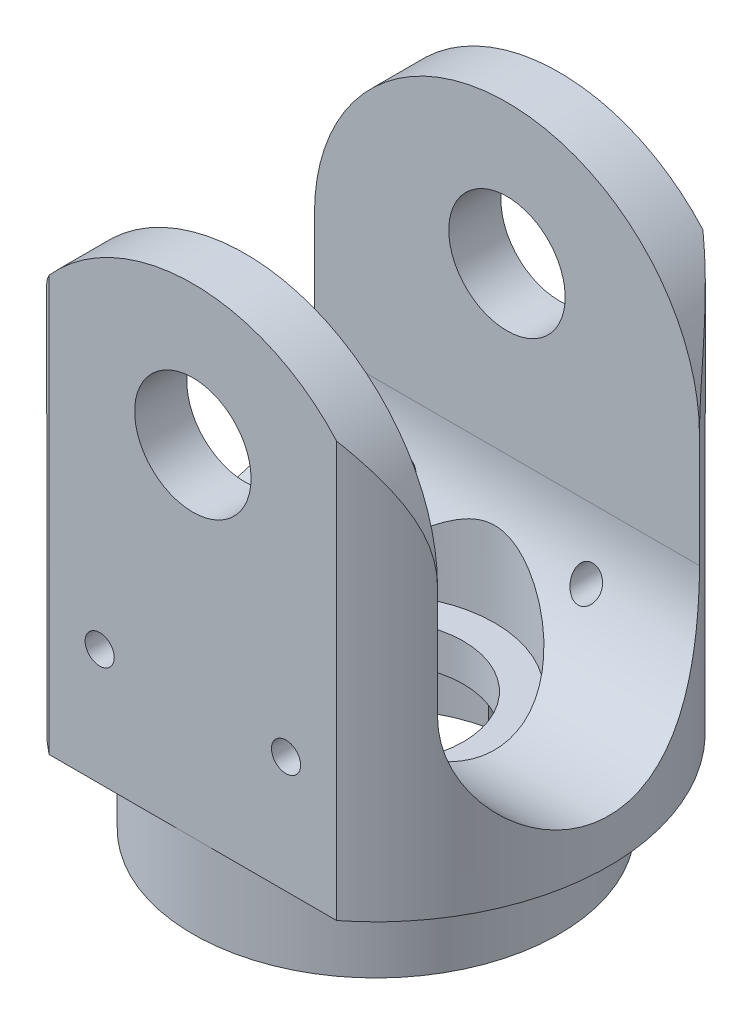
SolidWorks part; units mm, degrees
material "7075-T6 (SN)"
ref_plane "X-Y Datum" through (0, 0, 0) normal (0, 0, 1) x (1, 0, 0)
ref_plane "X-Z Datum" through (0, 0, 0) normal (0, 1, 0) x (1, 0, 0)
ref_plane "Y-Z Datum" through (0, 0, 0) normal (1, 0, 0) x (0, 0, -1)
sketch "Sketch1" plane through (0, 0, 0) normal (0, 1, 0) x (1, 0, 0)
  circle A0 centre (0, 0) radius 12.7
  dimension "D1" = 25.4
extrude "Boss-Extrude1" add sketch "Sketch1" along normal blind 15.367 and the other way blind 15.367
ref_plane "Plane2" through (0, 0, 9.9886) normal (0, 0, 1) x (1, 0, 0)
sketch "Sketch4" plane through (0, 0, 9.9886) normal (0, 0, 1) x (1, 0, 0)
  line L1 (-12.7, 15.367) -> (12.7, 15.367)
  line L2 (-12.7, 15.367) -> (-12.7, -15.367)
  line L3 (-12.7, -15.367) -> (12.7, -15.367)
  line L4 (12.7, 15.367) -> (12.7, -15.367)
extrude "Cut-Extrude2" cut sketch "Sketch4" along normal through all
mirror "Mirror2" about plane through (0, 0, 0) normal (0, 0, 1) of "Cut-Extrude2"
sketch "Sketch5" plane through (0, 0, 0) normal (1, 0, 0) x (0, 0, -1)
  line L0 (9.9886, 15.367) -> (-9.9886, 15.367) construction
  line L1 (-7.1437, 15.367) -> (7.1437, 15.367)
  line L2 (-7.1437, 15.367) -> (-7.1437, -1.27)
  line L3 (-7.1437, -1.27) -> (7.1438, -1.27)
  line L4 (7.1437, 15.367) -> (7.1438, -1.27)
  line L5 (0, 13.97) -> (0, -13.97) construction
  line L6 (0, -8.4138) -> (0, 15.367) construction
  arc A0 (-7.1437, -1.27) -> (7.1438, -1.27) centre (0, -1.27) ccw
  dimension "D3" = 16.637
  dimension "D4" = 23.7808
  dimension "D1" = 14.2875
  dimension "D2" = 7.1437
extrude "Cut-Extrude3" cut sketch "Sketch5" against normal through all both and the other way through all contours L6 A0 L3 | A0 L6 L3 | L2 L1 L4 L3 region at (0, -4.3019, 3.0319) region at (0, -4.3019, -3.0319)
sketch "Sketch6" plane through (0, 0, 9.9886) normal (0, 0, 1) x (1, 0, 0)
  line L0 (0, -43.0151) -> (0, 43.0151) construction
  line L1 (-7.8434, 15.367) -> (7.8434, 15.367) construction
  line L2 (10.5004, 4.8666) -> (14.8497, 4.8666)
  line L3 (-10.5004, 4.8666) -> (-14.8497, 4.8666)
  circle A0 centre (0, 4.8666) radius 10.5004
  arc A1 (14.8497, 4.8666) -> (-14.8497, 4.8666) centre (0, 4.8666) ccw
  line M2 (7.8434, 15.367) -> (-7.8434, 15.367)
  line M3 (-7.8434, 15.367) -> (-7.8434, -15.367)
  line M5 (7.8434, -15.367) -> (7.8434, 15.367)
  dimension "D1" = 21.0007
extrude "Cut-Extrude4" cut sketch "Sketch6" against normal through all contours L2 A1 L3 A0 M3 M2 M5 | A0 M2 M3 | A0 M5 M2 region at (10.124, 8.7197, 9.9886) region at (5.9543, 14.3505, 9.9886) region at (-5.9543, 14.3505, 9.9886)
sketch "Sketch7" plane through (0, -15.367, 0) normal (0, -1, 0) x (1, 0, 0)
  circle A0 centre (0, 0) radius 4.7625
  dimension "D1" = 9.525
extrude "Cut-Extrude5" cut sketch "Sketch7" against normal through all
sketch "Sketch9" plane through (0, -15.367, 0) normal (0, -1, 0) x (1, 0, 0)
  circle A0 centre (0, 0) radius 9.9822
  circle A1 centre (0, 0) radius 17.8528
  dimension "D1" = 19.9644
extrude "Cut-Extrude6" cut sketch "Sketch9" against normal blind 4.572
ref_plane "Plane3" through (0, 15.367, 0) normal (0, 1, 0) x (1, 0, 0)
sketch "Sketch10" plane through (0, 15.367, 0) normal (0, 1, 0) x (1, 0, 0)
  circle A0 centre (0, 0) radius 6.477
  dimension "D1" = 12.954
extrude "Cut-Extrude7" cut sketch "Sketch10" against normal blind 24.257
sketch "Sketch11" plane through (0, 0, 9.9886) normal (0, 0, 1) x (1, 0, 0)
  line L0 (-9.9822, -10.795) -> (9.9822, -10.795) construction
  line L1 (0, 7.747) -> (0, 0) construction
  circle A0 centre (0, 7.747) radius 3.175
  dimension "D1" = 6.35
  dimension "D2" = 18.542
extrude "Cut-Extrude8" cut sketch "Sketch11" against normal through all
sketch "Sketch12" plane through (0, 0, -9.9886) normal (0, 0, -1) x (-1, 0, 0)
  line L0 (-7.8434, -10.795) -> (7.8434, -10.795) construction
  line L1 (7.8434, 11.848) -> (7.8434, -10.795) construction
  line L2 (-7.8434, -10.795) -> (-7.8434, 11.848) construction
  circle A0 centre (5.0811, -4.445) radius 0.7938
  circle A1 centre (-5.0811, -4.445) radius 0.7938
  point P6 (-5.8749, -4.445)
  point P7 (5.8749, -4.445)
  dimension "D1" = 1.5875
  dimension "D2" = 1.5875
  dimension "D3" = 6.35
  dimension "D4" = 6.35
  dimension "D5" = 1.9685
  dimension "D6" = 1.9685
extrude "Cut-Extrude9" cut sketch "Sketch12" against normal through all both and the other way through all
sketch "Sketch13" plane through (0, -15.367, 0) normal (0, -1, 0) x (1, 0, 0)
  line L0 (-0.2399, -7.9974) -> (7.5971, -2.5099)
  line L1 (4.5892, -6.554) -> (0, 0) construction
  line L2 (-2.54, 0) -> (2.54, 0)
  circle A0 centre (0, 0) radius 8.001
  circle M5 centre (0, 0) radius 4.7625
  dimension "D1" = 16.002
  dimension "D2" = 35
  dimension "D3" = 6.4135
  dimension "D4" = 5.08
extrude "Cut-Extrude10" [suppressed] cut sketch "Sketch13" against normal blind 4.445 contours L0 A0 M5
sketch "Sketch14" [suppressed] plane through (0, -15.367, 0) normal (0, -1, 0) x (1, 0, 0)
  line L0 (0, 0) -> (-0.2399, -7.9974) construction
  line L1 (0, 0) -> (7.5971, -2.5099) construction
  circle A0 centre (-0.217, -7.2354) radius 1.5875
  circle A1 centre (6.8736, -2.2708) radius 1.5875
  dimension "D1" = 3.175
  dimension "D2" = 3.175
  dimension "D3" = 0.762
  dimension "D4" = 0.762
extrude "Cut-Extrude11" [suppressed] cut sketch "Sketch14" against normal up to surface (4.445 mm away) up to face at (0, -15.367, -4.7625)
sketch "Sketch15" plane through (0, -15.367, 0) normal (0, -1, 0) x (1, 0, 0)
  line L0 (-0.2399, -7.9974) -> (7.5971, -2.5099)
  line L1 (4.5892, -6.554) -> (0, 0) construction
  line L2 (-1.905, 0) -> (1.905, 0)
  circle A1 centre (0, 0) radius 9.9822 construction
  circle A2 centre (0, 0) radius 8.001
  circle M4 centre (0, 0) radius 4.7625
  dimension "D3" = 16.002
  dimension "D1" = 35
  dimension "D2" = 6.4135
  dimension "D4" = 3.81
extrude "Cut-Extrude12" cut sketch "Sketch15" against normal blind 4.445 contours A2 M4 region at (-5.4145, -15.367, 5.5794)
sketch "Sketch16" plane through (0, -15.367, 0) normal (0, -1, 0) x (1, 0, 0)
  line L0 (0, 0) -> (-0.2399, -7.9974) construction
  line L1 (0, 0) -> (7.5971, -2.5099) construction
  circle A4 centre (-0.217, -7.2354) radius 1.5875
  circle A5 centre (6.8736, -2.2708) radius 1.5875
  dimension "D1" = 3.175
  dimension "D4" = 0.762
  dimension "D2" = 3.175
  dimension "D3" = 0.762
extrude "Cut-Extrude13" cut sketch "Sketch16" against normal up to surface (4.445 mm away) up to face at (0, -10.922, -4.7625)
sketch "Pick Up Point" plane through (0, 0, 0) normal (0, 0, 1) x (1, 0, 0)
  point P0 (0, 7.747)
ref_plane "Plane4" through (0, 15.367, -7.1437) normal (0, 1, 0) x (1, 0, 0)
sketch "Sketch20" plane through (0, 15.367, -7.1437) normal (0, 1, 0) x (1, 0, 0)
  circle A0 centre (0, -7.1437) radius 12.7
  point P3 (0, 5.5562)
  point P4 (0, -19.8438)
  point P6 (0, -7.1437)
  dimension "D1" = 25.4
ref_plane "Plane5" through (0, -15.367, 0) normal (0, -1, 0) x (-1, 0, 0)
sketch "Sketch21" plane through (0, -15.367, 0) normal (0, -1, 0) x (-1, 0, 0)
  point P0 (0, 0)
ref_point "Point1"
ref_point "Point2"
ref_point "Point3"
ref_point "Point4"
ref_point "Point5"
ref_axis "Axis1" [suppressed] through (0, -8.89, 0) along (0, -1, 0)
sketch "Sketch22" plane through (0, 0, 9.9886) normal (0, 0, 1) x (1, 0, 0)
  arc A0 (7.8434, 11.848) -> (-7.8434, 11.848) centre (0, 4.8666) ccw construction
  point P0 (0, 15.367)
sketch "Sketch23" plane through (0, -10.922, 0) normal (0, -1, 0) x (1, 0, 0)
  line L0 (-1.693, -7.8198) -> (7.9273, -1.0834)
  arc A0 (7.9273, -1.0834) -> (-1.693, -7.8198) centre (0, 0) ccw
